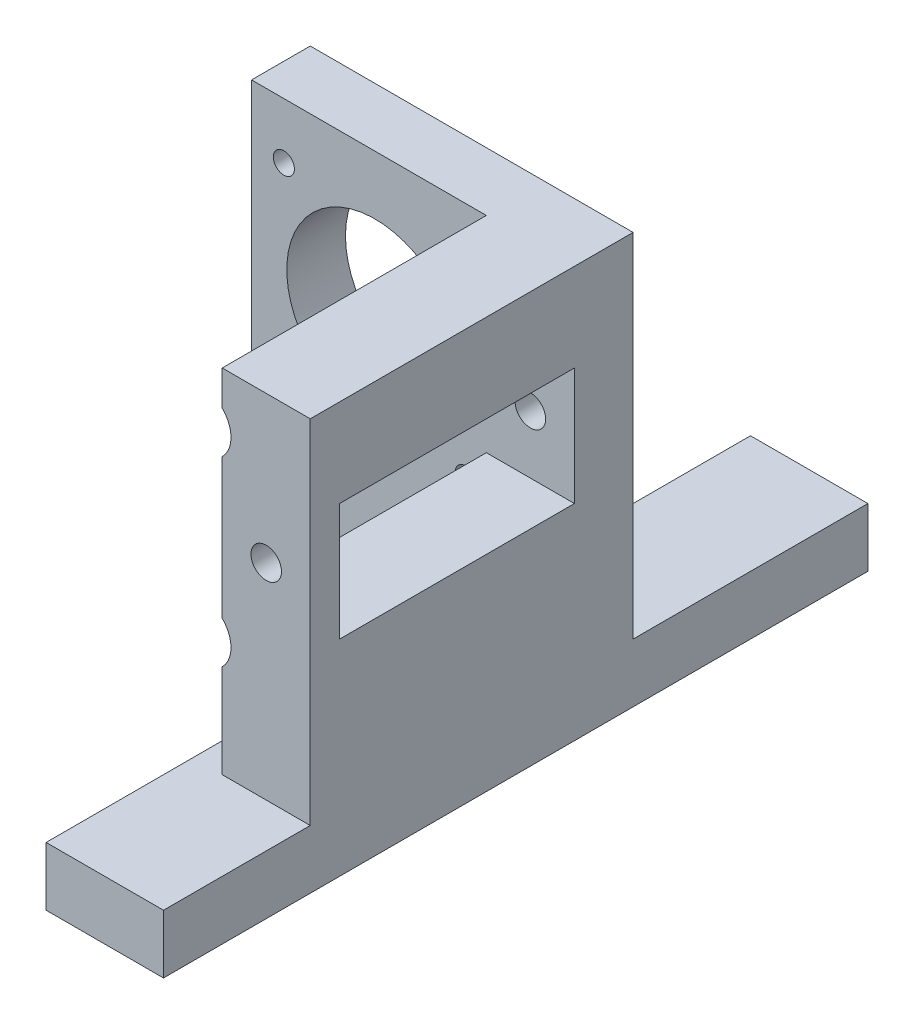
SolidWorks part; units mm, degrees
ref_plane "Front Plane" through (0, 0, 0) normal (0, 0, 1) x (1, 0, 0)
ref_plane "Top Plane" through (0, 0, 0) normal (0, 1, 0) x (1, 0, 0)
ref_plane "Right Plane" through (0, 0, 0) normal (1, 0, 0) x (0, 0, -1)
sketch "Sketch4" plane through (0, 0, 0) normal (0, 1, 0) x (1, 0, 0)
  line L1 (0, 0) -> (40, 0)
  line L2 (0, 0) -> (0, 80)
  line L3 (0, 80) -> (40, 80)
  line L4 (40, 0) -> (40, 80)
  dimension "D1" = 80
  dimension "D2" = 40
extrude "Boss-Extrude4" add sketch "Sketch4" along normal blind 5
sketch "Sketch5" plane through (0, 5, 0) normal (0, 1, 0) x (1, 0, 0)
  line L0 (40, 40) -> (30, 40)
  line L1 (30, 30) -> (30, 50) construction
  line L2 (40, 50) -> (30, 50)
  line L3 (30, 50) -> (30, 55)
  line L4 (0, 80) -> (0, 0)
  line L5 (0, 0) -> (40, 0)
  line L6 (40, 0) -> (40, 80)
  line L7 (40, 80) -> (0, 80)
  line L8 (0, 80) -> (0, 0)
  line L9 (0, 0) -> (40, 0)
  line L10 (40, 0) -> (40, 80)
  line L11 (40, 80) -> (0, 80)
  line L12 (30, 55) -> (40, 55)
  line L13 (40, 55) -> (40, 50)
  line L14 (40, 30) -> (30, 30)
  line L15 (30, 30) -> (30, 25)
  line L16 (30, 25) -> (40, 25)
  line L17 (40, 25) -> (40, 30)
  point P9 (30, 40)
  line M11 (40, 0) -> (40, 80)
  dimension "D2" = 10
  dimension "D3" = 10
  dimension "D4" = 5
  dimension "D5" = 5
  dimension "D1" = 0
extrude "Boss-Extrude6" add sketch "Sketch5" along normal blind 50 contours L12 L3 L2 M11 | L15 L16 L10 L14 region at (35, 5, -52.5) region at (35, 5, -27.5)
sketch "Sketch7" plane through (0, 0, -50) normal (0, 0, 1) x (1, 0, 0)
  line L1 (30, 5) -> (40, 5)
  line L2 (30, 5) -> (30, 30)
  line L3 (30, 30) -> (40, 30)
  line L4 (40, 5) -> (40, 30)
  line L5 (40, 55) -> (40, 5) construction
  line L7 (30, 55) -> (40, 55)
  line L8 (30, 55) -> (30, 50)
  line L9 (30, 50) -> (40, 50)
  line L10 (40, 55) -> (40, 50)
  dimension "D1" = 25
  dimension "D2" = 10
  dimension "D3" = 5
extrude "Boss-Extrude7" add sketch "Sketch7" along normal up to surface (20 mm away) contours L8 L7 L10 L9 | L2 L1 L4 L3 up to face at (35, 30, -30)
sketch "Sketch8" plane through (0, 0, -80) normal (0, 0, -1) x (-1, 0, 0)
  line L4 (-40, 0) -> (0, 0)
  line L5 (0, 0) -> (0, 5)
  line L6 (0, 5) -> (-40, 5)
  line L7 (-40, 5) -> (-40, 0)
  line L8 (-40, 0) -> (0, 0)
  line L9 (0, 0) -> (0, 5)
  line L10 (0, 5) -> (-40, 5)
  line L11 (-40, 5) -> (-40, 0)
  dimension "D1" = 0
extrude "Boss-Extrude8" add sketch "Sketch8" along normal blind 20 contours L8 L9 L10 L11
sketch "Sketch9" plane through (0, 0, 0) normal (-1, 0, 0) x (0, 0, 1)
  line L4 (-100, 0) -> (0, 0)
  line L5 (0, 0) -> (0, 5)
  line L6 (0, 5) -> (-100, 5)
  line L7 (-100, 5) -> (-100, 0)
  line L8 (-100, 0) -> (0, 0)
  line L9 (0, 0) -> (0, 5)
  line L10 (0, 5) -> (-100, 5)
  line L11 (-100, 5) -> (-100, 0)
  dimension "D1" = 0
extrude "Boss-Extrude9" add sketch "Sketch9" along normal blind 10
sketch "Sketch10" plane through (30, 0, 0) normal (-1, 0, 0) x (0, 0, 1)
  line L0 (-25, 5) -> (-55, 5) construction
  line L1 (-55, 55) -> (-50, 55)
  line L2 (-55, 55) -> (-55, 5)
  line L3 (-55, 5) -> (-50, 5)
  line L4 (-50, 55) -> (-50, 5)
  dimension "D1" = 5
extrude "Boss-Extrude10" add sketch "Sketch10" along normal blind 40 contours L2 L1 L4 L3
sketch "Sketch11" plane through (0, 55, 0) normal (0, 1, 0) x (1, 0, 0)
  line L6 (40, 55) -> (-10, 55)
  line L7 (-10, 55) -> (-10, 50)
  line L8 (-10, 50) -> (30, 50)
  line L9 (30, 50) -> (30, 25)
  line L10 (30, 25) -> (40, 25)
  line L11 (40, 25) -> (40, 55)
  line L12 (40, 55) -> (-10, 55)
  line L13 (-10, 55) -> (-10, 50)
  line L14 (-10, 50) -> (30, 50)
  line L15 (30, 50) -> (30, 25)
  line L16 (30, 25) -> (40, 25)
  line L17 (40, 25) -> (40, 55)
  dimension "D1" = 0
extrude "Boss-Extrude11" add sketch "Sketch11" along normal blind 10
sketch "Sketch12" plane through (0, 0, -50) normal (0, 0, 1) x (1, 0, 0)
  line L0 (30, 50) -> (30, 30)
  line L1 (30, 40) -> (26, 40)
  line L2 (0.3934, 50.6066) -> (-3.227, 54.227)
  line L3 (-10, 61) -> (32, 61)
  line L4 (-10, 61) -> (-10, 19)
  line L5 (-10, 19) -> (32, 19)
  line L6 (32, 61) -> (32, 19)
  line L7 (-10, 61) -> (32, 19) construction
  line L8 (30, 30) -> (40, 30)
  line L9 (40, 30) -> (40, 50)
  line L10 (40, 50) -> (30, 50)
  line L11 (30, 50) -> (30, 65)
  line L12 (30, 65) -> (-10, 65)
  line L13 (-10, 65) -> (-10, 5)
  line L14 (-10, 5) -> (30, 5)
  line L15 (30, 5) -> (30, 30)
  line L16 (30, 30) -> (40, 30)
  line L17 (40, 30) -> (40, 50)
  line L18 (40, 50) -> (30, 50)
  line L19 (30, 50) -> (30, 65)
  line L20 (30, 65) -> (-10, 65)
  line L21 (-10, 65) -> (-10, 5)
  line L22 (-10, 5) -> (30, 5)
  line L23 (30, 5) -> (30, 30)
  line L24 (-10, 19) -> (32, 61) construction
  line L25 (-2.6998, 24.5002) -> (-4.4998, 24.5002) construction
  line L26 (24.6998, 24.5002) -> (-2.6998, 24.5002)
  line L27 (26.4998, 26.3002) -> (26.4998, 53.6998)
  line L28 (24.6998, 55.4998) -> (-2.6998, 55.4998)
  line L29 (-4.4998, 26.3002) -> (-4.4998, 53.6998)
  line L30 (26.4998, 24.5002) -> (-4.4998, 55.4998) construction
  line L31 (26.4998, 55.4998) -> (-4.4998, 24.5002) construction
  line L32 (26.4998, 24.5002) -> (24.6998, 24.5002) construction
  line L33 (26.4998, 24.5002) -> (26.4998, 26.3002) construction
  line L34 (26.4998, 53.6998) -> (26.4998, 55.4998) construction
  line L35 (26.4998, 55.4998) -> (24.6998, 55.4998) construction
  line L36 (11, 40) -> (0.3934, 50.6066) construction
  line L37 (26, 40) -> (11, 40) construction
  line L38 (-3.227, 54.227) -> (-4.4998, 55.4998) construction
  line L39 (-4.4998, 53.6998) -> (-4.4998, 55.4998) construction
  line L40 (-2.6998, 55.4998) -> (-4.4998, 55.4998) construction
  line L41 (-4.4998, 24.5002) -> (-4.4998, 26.3002) construction
  circle A0 centre (11, 40) radius 15
  circle A1 centre (-4.4998, 55.4998) radius 1.8
  circle A2 centre (26.4998, 55.4998) radius 1.8
  circle A3 centre (26.4998, 24.5002) radius 1.8
  circle A4 centre (-4.4998, 24.5002) radius 1.8
  dimension "D2" = 19
  dimension "D3" = 30
  dimension "D6" = 3.6
  dimension "D7" = 3.6
  dimension "D1" = 0
  dimension "D4" = 42
  dimension "D5" = 21.92
extrude "Cut-Extrude1" cut sketch "Sketch12" against normal up to surface (5 mm away) contours A0 | A1 | A2 | A4 | A3 region at (11, 40, -50) region at (-4.4998, 55.4998, -50) up to face at (15, 35, -55)
sketch "Sketch13" plane through (0, 0, -50) normal (0, 0, 1) x (1, 0, 0)
  line L0 (40, 40) -> (35, 40) construction
  line L8 (30, 30) -> (40, 30)
  line L9 (40, 30) -> (40, 50)
  line L10 (40, 50) -> (30, 50)
  line L11 (30, 50) -> (30, 65)
  line L12 (30, 65) -> (-10, 65)
  line L13 (-10, 65) -> (-10, 5)
  line L14 (-10, 5) -> (30, 5)
  line L15 (30, 5) -> (30, 30)
  line L16 (30, 30) -> (40, 30)
  line L17 (40, 30) -> (40, 50)
  line L18 (40, 50) -> (30, 50)
  line L19 (30, 50) -> (30, 65)
  line L20 (30, 65) -> (-10, 65)
  line L21 (-10, 65) -> (-10, 5)
  line L22 (-10, 5) -> (30, 5)
  line L23 (30, 5) -> (30, 30)
  circle A0 centre (35, 40) radius 2.25
  dimension "D3" = 4.5
  dimension "D2" = 5
  dimension "D1" = 0
extrude "Cut-Extrude2" cut sketch "Sketch13" against normal through all both and the other way through all contours A0
sketch "Sketch14" plane through (0, 0, -25) normal (0, 0, 1) x (1, 0, 0)
  circle A0 centre (35, 40) radius 2.25 construction
  circle A1 centre (35, 40) radius 2.25
  circle A2 centre (35, 40) radius 4
  dimension "D1" = 8
extrude "Cut-Extrude4" cut sketch "Sketch14" against normal blind 2 contours A1 | A2
sketch "Sketch15" plane through (0, 0, -55) normal (0, 0, -1) x (-1, 0, 0)
  circle A0 centre (-35, 40) radius 2.25 construction
  circle A1 centre (-35, 40) radius 2.25
  circle A2 centre (-35, 40) radius 4
  dimension "D1" = 8
extrude "Cut-Extrude5" cut sketch "Sketch15" against normal blind 2
sketch "Sketch17" plane through (0, 0, -25) normal (0, 0, 1) x (1, 0, 0)
  line L0 (26.4998, 55.4998) -> (26.4998, 24.5002)
  circle A0 centre (26.4998, 55.4998) radius 1.8 construction
  circle A1 centre (26.4998, 55.4998) radius 1.8
  circle A2 centre (26.4998, 55.4998) radius 5
  circle A3 centre (26.4998, 24.5002) radius 5
  line M4 (30, 65) -> (30, 5)
  dimension "D1" = 10
  dimension "D2" = 10
extrude "Cut-Extrude6" cut sketch "Sketch17" against normal up to surface (25 mm away) contours A2 A1 M4 | A3 M4 | A3 M4 | A2 M4 region at (21.9924, 57.3406, -25) region at (26.0733, 24.5002, -25) region at (30.6084, 55.4998, -25) region at (30.6084, 24.5002, -25) up to face at (37.25, 40, -50)
sketch "Sketch19" plane through (0, 0, -55) normal (0, 0, -1) x (-1, 0, 0)
  line L4 (10, 5) -> (10, 65)
  line L5 (10, 65) -> (-40, 65)
  line L6 (-40, 65) -> (-40, 5)
  line L7 (-40, 5) -> (10, 5)
  line L8 (10, 5) -> (10, 65)
  line L9 (10, 65) -> (-40, 65)
  line L10 (-40, 65) -> (-40, 5)
  line L11 (-40, 5) -> (10, 5)
  circle A0 centre (4.4998, 55.4998) radius 1.8 construction
  circle A1 centre (4.4998, 24.5002) radius 1.8 construction
  circle A2 centre (-26.4998, 24.5002) radius 1.8 construction
  circle A3 centre (-11, 40) radius 15 construction
  circle A4 centre (-35, 40) radius 4 construction
  circle A6 centre (-26.4998, 55.4998) radius 1.8 construction
  circle A7 centre (4.4998, 55.4998) radius 1.8
  circle A8 centre (4.4998, 24.5002) radius 1.8
  circle A9 centre (-26.4998, 24.5002) radius 1.8
  circle A10 centre (-11, 40) radius 15
  circle A11 centre (-35, 40) radius 4
  circle A13 centre (-26.4998, 55.4998) radius 1.8
  dimension "D1" = 0
extrude "Boss-Extrude13" add sketch "Sketch19" along normal blind 5
sketch "Sketch20" plane through (0, 0, -53) normal (0, 0, -1) x (-1, 0, 0)
  circle A0 centre (-35, 40) radius 2.25 construction
  circle A1 centre (-35, 40) radius 4
  circle A2 centre (-35, 40) radius 4
  circle A3 centre (-35, 40) radius 2.25
  dimension "D1" = 0
extrude "Boss-Extrude14" add sketch "Sketch20" along normal blind 5
sketch "Sketch21" plane through (40, 0, 0) normal (1, 0, 0) x (0, 0, -1)
  line L0 (50, 50) -> (50, 30) construction
  line L1 (30, 50) -> (30, 30) construction
  line L2 (30, 50) -> (50, 50) construction
  line L3 (30, 30) -> (50, 30) construction
  line L4 (50, 50) -> (50, 30)
  line L5 (30, 50) -> (30, 30)
  line L6 (30, 50) -> (50, 50)
  line L7 (30, 30) -> (50, 30)
  line L8 (100, 5) -> (60, 5)
  line L9 (60, 5) -> (60, 65)
  line L10 (60, 65) -> (25, 65)
  line L11 (25, 65) -> (25, 5)
  line L12 (25, 5) -> (0, 5)
  line L13 (0, 5) -> (0, 0)
  line L14 (0, 0) -> (100, 0)
  line L15 (100, 0) -> (100, 5)
  line L16 (100, 5) -> (60, 5)
  line L17 (60, 5) -> (60, 65)
  line L18 (60, 65) -> (25, 65)
  line L19 (25, 65) -> (25, 5)
  line L20 (25, 5) -> (0, 5)
  line L21 (0, 5) -> (0, 0)
  line L22 (0, 0) -> (100, 0)
  line L23 (100, 0) -> (100, 5)
  dimension "D1" = 0
extrude "Boss-Extrude15" add sketch "Sketch21" along normal blind 5
sketch "Sketch22" plane through (0, 0, -60) normal (0, 0, -1) x (-1, 0, 0)
  circle A0 centre (-35, 40) radius 4 construction
  circle A1 centre (-35, 40) radius 4
extrude "Boss-Extrude16" add sketch "Sketch22" against normal up to surface (10 mm away) up to face at (26.0833, 38.3333, -50)
sketch "Sketch23" plane through (0, 0, -25) normal (0, 0, 1) x (1, 0, 0)
  circle A0 centre (35, 40) radius 4 construction
  circle A1 centre (35, 40) radius 4
extrude "Boss-Extrude17" add sketch "Sketch23" against normal up to surface (5 mm away) up to face at (37.25, 40, -30)
sketch "Sketch24" plane through (0, 0, -30) normal (0, 0, -1) x (-1, 0, 0)
  line L0 (-30, 30) -> (-45, 50) construction
  line L1 (-30, 50) -> (-45, 30) construction
  line L4 (-30, 50) -> (-45, 50)
  line L5 (-45, 50) -> (-45, 30)
  line L6 (-45, 30) -> (-30, 30)
  line L7 (-30, 30) -> (-30, 50)
  line L8 (-30, 50) -> (-45, 50)
  line L9 (-45, 50) -> (-45, 30)
  line L10 (-45, 30) -> (-30, 30)
  line L11 (-30, 30) -> (-30, 50)
  circle A0 centre (-37.5, 40) radius 2.6
  dimension "D2" = 5.2
  dimension "D1" = 0
extrude "Cut-Extrude7" cut sketch "Sketch24" against normal through all both and the other way through all contours A0
sketch "Sketch25" plane through (0, 0, 0) normal (0, -1, 0) x (1, 0, 0)
  line L4 (45, 0) -> (-10, 0)
  line L5 (-10, 0) -> (-10, -100)
  line L6 (-10, -100) -> (45, -100)
  line L7 (45, -100) -> (45, 0)
  line L8 (45, 0) -> (-10, 0)
  line L9 (-10, 0) -> (-10, -100)
  line L10 (-10, -100) -> (45, -100)
  line L11 (45, -100) -> (45, 0)
  dimension "D1" = 0
extrude "Boss-Extrude18" add sketch "Sketch25" along normal blind 5
sketch "Sketch26" plane through (0, 0, 0) normal (0, 0, 1) x (1, 0, 0)
  line L4 (-10, 5) -> (-10, -5)
  line L5 (-10, -5) -> (45, -5)
  line L6 (45, -5) -> (45, 5)
  line L7 (45, 5) -> (-10, 5)
  line L8 (-10, 5) -> (-10, -5)
  line L9 (-10, -5) -> (45, -5)
  line L10 (45, -5) -> (45, 5)
  line L11 (45, 5) -> (-10, 5)
  dimension "D1" = 0
extrude "Boss-Extrude19" add sketch "Sketch26" along normal blind 20
sketch "Sketch27" plane through (30, 0, 0) normal (-1, 0, 0) x (0, 0, 1)
  line L1 (-30, 50) -> (-25, 50)
  line L2 (-30, 50) -> (-30, 30)
  line L3 (-30, 30) -> (-25, 30)
  line L4 (-25, 50) -> (-25, 30)
  line L5 (-25, 51.9293) -> (-25, 28.0707) construction
  dimension "D1" = 5
  dimension "D2" = 20
extrude "Cut-Extrude8" cut sketch "Sketch27" against normal blind 15
sketch "Sketch28" plane through (0, 0, -25) normal (0, 0, 1) x (1, 0, 0)
  line L5 (45, 5) -> (45, 30)
  line L6 (45, 30) -> (30, 30)
  line L7 (30, 30) -> (30, 28.0707)
  line L8 (30, 20.9297) -> (30, 5)
  line L9 (30, 5) -> (45, 5)
  line L10 (45, 5) -> (45, 30)
  line L11 (45, 30) -> (30, 30)
  line L12 (30, 30) -> (30, 28.0707)
  line L13 (30, 20.9297) -> (30, 5)
  line L14 (30, 5) -> (45, 5)
  line L15 (30, 51.9293) -> (30, 50)
  line L16 (30, 50) -> (45, 50)
  line L17 (45, 50) -> (45, 65)
  line L18 (45, 65) -> (30, 65)
  line L19 (30, 65) -> (30, 59.0703)
  line L20 (30, 51.9293) -> (30, 50)
  line L21 (30, 50) -> (45, 50)
  line L22 (45, 50) -> (45, 65)
  line L23 (45, 65) -> (30, 65)
  line L24 (30, 65) -> (30, 59.0703)
  arc A1 (30, 20.9297) -> (30, 28.0707) centre (26.4998, 24.5002) ccw
  arc A2 (30, 20.9297) -> (30, 28.0707) centre (26.4998, 24.5002) ccw
  arc A3 (30, 51.9293) -> (30, 59.0703) centre (26.4998, 55.4998) ccw
  arc A4 (30, 51.9293) -> (30, 59.0703) centre (26.4998, 55.4998) ccw
  dimension "D1" = 0
  dimension "D2" = 0
extrude "Boss-Extrude20" add sketch "Sketch28" along normal blind 20
sketch "Sketch29" plane through (0, 30, 0) normal (0, 1, 0) x (1, 0, 0)
  line L7 (30, 5) -> (45, 5)
  line L8 (30, 5) -> (30, 10)
  line L9 (30, 10) -> (45, 10)
  line L10 (45, 5) -> (45, 10)
  line L11 (45, 5) -> (45, 50) construction
  dimension "D1" = 5
  dimension "D2" = 15
extrude "Boss-Extrude21" add sketch "Sketch29" along normal blind 20
sketch "Sketch30" plane through (0, 0, -60) normal (0, 0, -1) x (-1, 0, 0)
  circle A0 centre (-37.5, 40) radius 2.6 construction
  circle A1 centre (-37.5, 40) radius 2.6
extrude "Cut-Extrude9" cut sketch "Sketch30" against normal blind 60
sketch "Sketch31" plane through (0, 5, 0) normal (0, 1, 0) x (1, 0, 0)
  line L0 (25, -20) -> (25, 50)
  line L1 (25, -450) -> (25, 100) construction
  line L2 (25, 60) -> (25, 100)
  line L4 (-10, 100) -> (-10, 60)
  line L5 (-10, 60) -> (45, 60)
  line L6 (45, 60) -> (45, 100)
  line L7 (45, 100) -> (-10, 100)
  line L8 (-10, 100) -> (-10, 60)
  line L9 (-10, 60) -> (25, 60)
  line L11 (25, 100) -> (-10, 100)
  line L14 (45, 5) -> (30, 5)
  line L15 (30, 5) -> (30, 50)
  line L16 (30, 50) -> (-10, 50)
  line L17 (-10, 50) -> (-10, -20)
  line L18 (-10, -20) -> (45, -20)
  line L19 (45, -20) -> (45, 5)
  line L22 (25, 50) -> (-10, 50)
  line L23 (-10, 50) -> (-10, -20)
  line L24 (-10, -20) -> (25, -20)
  dimension "D3" = 35
  dimension "D1" = 0
  dimension "D2" = 0
extrude "Cut-Extrude10" cut sketch "Sketch31" against normal blind 10
